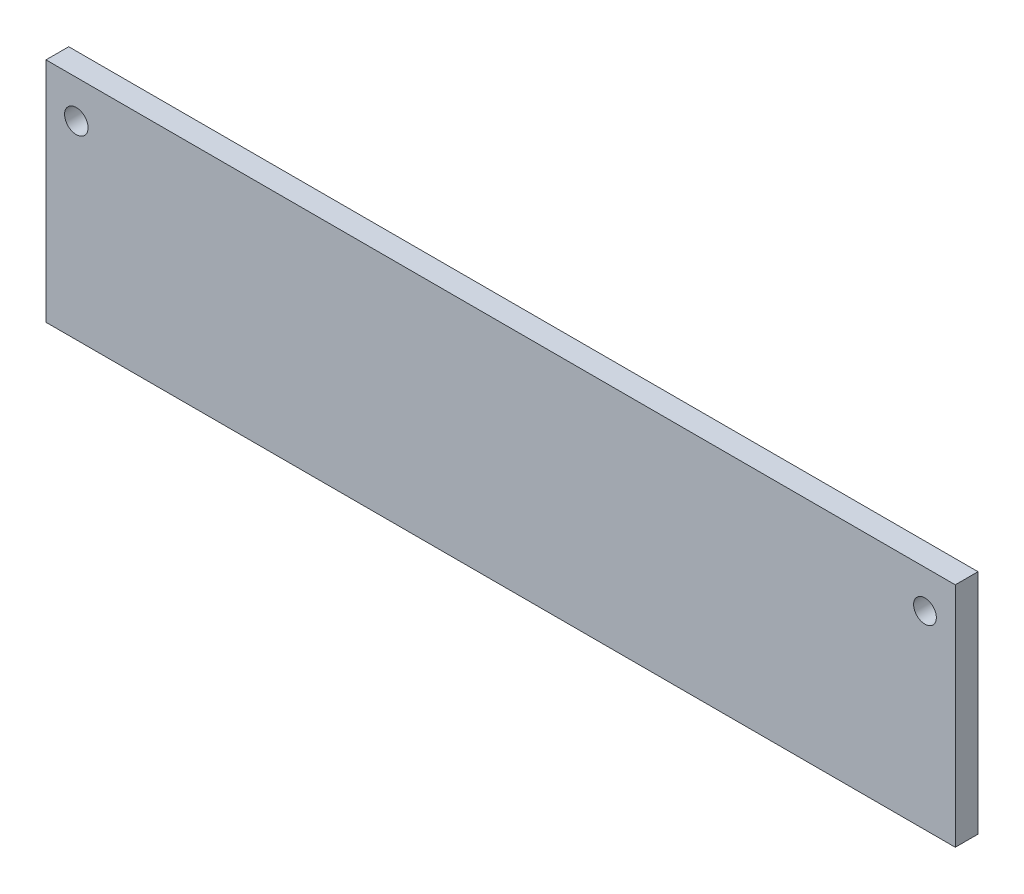
SolidWorks part; units mm, degrees
ref_plane "前视基准面" through (0, 0, 0) normal (0, 0, 1) x (1, 0, 0)
ref_plane "上视基准面" through (0, 0, 0) normal (0, 1, 0) x (1, 0, 0)
ref_plane "右视基准面" through (0, 0, 0) normal (1, 0, 0) x (0, 0, -1)
other "Configuration Table"
sketch "草图1" plane through (0, 0, 0) normal (0, 0, 1) x (1, 0, 0)
  line L1 (60, -15) -> (-60, -15)
  line L2 (60, -15) -> (60, 15)
  line L3 (60, 15) -> (-60, 15)
  line L4 (-60, -15) -> (-60, 15)
  line L5 (60, -15) -> (-60, 15) construction
  line L6 (60, 15) -> (-60, -15) construction
  point P0 (0, 0)
  dimension "D1" = 120
  dimension "D2" = 30
extrude "凸台-拉伸1" add sketch "草图1" along normal blind 3
sketch "草图3" plane through (0, 0, 0) normal (0, 0, -1) x (-1, 0, 0)
  line L2 (60, 15) -> (60, -15) construction
  line L3 (-60, 15) -> (60, 15) construction
  line L5 (-60, -15) -> (-60, 15) construction
  circle A0 centre (-56, 10) radius 1.5
  circle A1 centre (56, 10) radius 1.55
  point P10 (80.5695, 9.4417)
  point P15 (-78.4713, 21.9258)
  dimension "D1" = 4
  dimension "D2" = 5
  dimension "D3" = 4
  dimension "D4" = 5
extrude "切除-拉伸2" cut sketch "草图3" against normal blind 10
